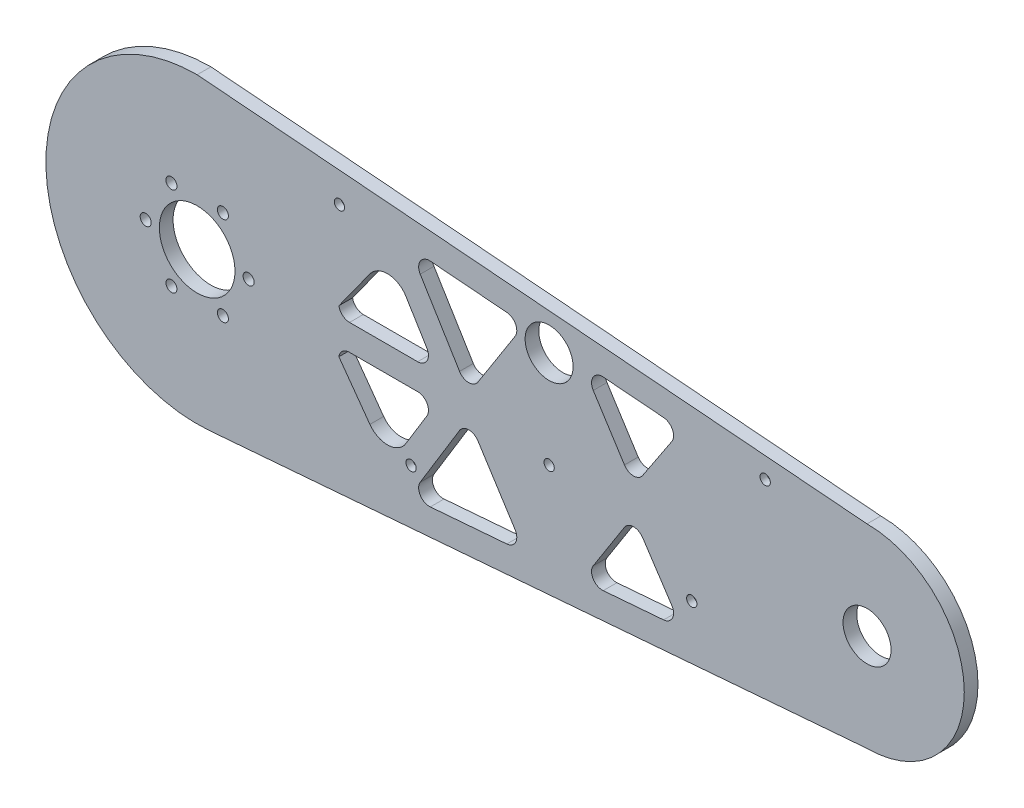
SolidWorks part; units mm, degrees
other "Marca1"
sketch "Croquis3" plane through (-70, -70, 6.35) normal (0, 0, 1) x (1, 0, 0)
material "6061-O (SS)"
ref_plane "Front Plane" through (0, 0, 0) normal (0, 0, 1) x (1, 0, 0)
ref_plane "Top Plane" through (0, 0, 0) normal (0, 1, 0) x (1, 0, 0)
ref_plane "Right Plane" through (0, 0, 0) normal (1, 0, 0) x (0, 0, -1)
sketch "Sketch1" plane through (0, 0, 0) normal (0, 0, 1) x (1, 0, 0)
  line L0 (0, 70) -> (310, 45)
  line L1 (5.1714, -69.8087) -> (310, -45)
  line L2 (0, 0) -> (310, 0) construction
  line L3 (107.899, 49.2595) -> (143.3142, 46.4034)
  line L4 (70.5232, 6) -> (102.03, 6)
  line L5 (219.6238, 32.8105) -> (206.1309, 12.4175)
  line L6 (197.7459, 12.4871) -> (183.2969, 35.1335)
  line L7 (162.8785, 6) -> (162.8785, -6) construction
  line L8 (258.6323, 64.5867) -> (258.6323, 39.5867) construction
  line L9 (147.1275, 38.7303) -> (129.9162, 11.7546)
  line L10 (121.433, 11.8395) -> (103.229, 41.6712)
  line L11 (98.117, 50.0484) -> (42.0027, 50.0484) construction
  line L12 (187.9139, 42.8067) -> (215.8558, 40.5533)
  line L13 (162.8785, 44.8257) -> (162.8785, 6) construction
  line L14 (67.1248, 64.5867) -> (162.8785, 40) construction
  line L15 (201.8849, 6) -> (201.8849, 41.68) construction
  line L16 (125.6066, 5) -> (125.6066, 47.8315) construction
  line L17 (96.5904, 29.5131) -> (106.2981, 13.6045)
  line L18 (125.6066, -5) -> (125.6066, -47.8315) construction
  line L19 (201.8849, -6) -> (201.8849, -41.68) construction
  line L20 (162.8785, -44.8257) -> (162.8785, -6) construction
  line L21 (98.117, -50.0484) -> (42.0027, -50.0484) construction
  line L22 (96.5904, -29.5131) -> (106.2981, -13.6045)
  line L23 (67.1248, 64.5867) -> (409.6974, 64.5867) construction
  line L24 (187.9139, -42.8067) -> (215.8558, -40.5533)
  line L25 (121.433, -11.8395) -> (103.229, -41.6712)
  line L26 (147.1275, -38.7303) -> (129.9162, -11.7546)
  line L27 (162.8785, 0) -> (258.6323, 64.5867) construction
  line L28 (67.1248, 64.5867) -> (67.1248, 39.5867) construction
  line L29 (197.7459, -12.4871) -> (183.2969, -35.1335)
  line L30 (219.6238, -32.8105) -> (206.1309, -12.4175)
  line L31 (70.5232, -6) -> (102.03, -6)
  line L32 (107.899, -49.2595) -> (143.3142, -46.4034)
  line L33 (0, -6.35) -> (0, 6.35) construction
  line L34 (67.1248, 39.5867) -> (162.8785, 40) construction
  line L35 (162.8785, 40) -> (68.3705, 24.1395) construction
  line L36 (79.9417, 30.1512) -> (65.583, 10.2294)
  line L37 (79.9417, -30.1512) -> (65.583, -10.2294)
  arc A0 (65.583, 10.2294) -> (70.5232, 6) centre (70.5232, 11) ccw
  arc A1 (310, -45) -> (310, 45) centre (310, 0) ccw
  circle A2 centre (0, 0) radius 14.2938
  circle A3 centre (310, 0) radius 11.115
  arc A4 (79.9417, 30.1512) -> (96.5904, 29.5131) centre (88.0542, 24.3041) cw
  arc A5 (96.5904, -29.5131) -> (79.9417, -30.1512) centre (88.0542, -24.3041) cw
  arc A6 (0, 70) -> (5.1714, -69.8087) centre (0, 0) ccw
  arc A7 (187.9139, 42.8067) -> (183.2969, 35.1335) centre (187.512, 37.8229) ccw
  arc A8 (219.6238, 32.8105) -> (215.8558, 40.5533) centre (215.4539, 35.5695) ccw
  arc A9 (206.1309, 12.4175) -> (197.7459, 12.4871) centre (201.961, 15.1765) cw
  circle A10 centre (162.8785, 40) radius 11.1125
  arc A13 (102.03, 6) -> (106.2981, 13.6045) centre (102.03, 11) ccw
  arc A14 (121.433, 11.8395) -> (129.9162, 11.7546) centre (125.7011, 14.444) ccw
  arc A15 (147.1275, 38.7303) -> (143.3142, 46.4034) centre (142.9123, 41.4196) ccw
  arc A16 (107.899, 49.2595) -> (103.229, 41.6712) centre (107.4971, 44.2757) ccw
  arc A17 (107.899, -49.2595) -> (103.229, -41.6712) centre (107.4971, -44.2757) cw
  arc A18 (147.1275, -38.7303) -> (143.3142, -46.4034) centre (142.9123, -41.4196) cw
  arc A19 (121.433, -11.8395) -> (129.9162, -11.7546) centre (125.7011, -14.444) cw
  arc A20 (102.03, -6) -> (106.2981, -13.6045) centre (102.03, -11) cw
  arc A24 (206.1309, -12.4175) -> (197.7459, -12.4871) centre (201.961, -15.1765) ccw
  arc A25 (219.6238, -32.8105) -> (215.8558, -40.5533) centre (215.4539, -35.5695) cw
  arc A26 (187.9139, -42.8067) -> (183.2969, -35.1335) centre (187.512, -37.8229) cw
  arc A29 (65.583, -10.2294) -> (70.5232, -6) centre (70.5232, -11) cw
  point P31 (177.8851, 43.6155)
  point P42 (187.6504, 6)
  point P44 (88.7465, 42.3671)
  point P45 (138.1067, 6)
  point P79 (88.7465, -42.3671)
  point P100 (138.1067, -6)
  point P101 (187.6504, -6)
  point P102 (177.8851, -43.6155)
  point P104 (0, 0)
  point P114 (310, 0)
  point P119 (0.2114, 0.3175)
  dimension "D2" = 45
  dimension "D3" = 12.7
  dimension "D4" = 22.23
  dimension "D6" = 12
  dimension "D11" = 5
  dimension "D12" = 70
  dimension "D13" = 25
  dimension "D8" = 5
  dimension "D14" = 12
  dimension "D15" = 25
  dimension "D16" = 310
  dimension "D17" = 22.225
  dimension "D5" = 28.5877
  dimension "D19" = 10
  dimension "D20" = 10
  dimension "D7" = 6
  dimension "D9" = 9.279
  dimension "D10" = 34
  dimension "D18" = 40
extrude "Boss-Extrude1" add sketch "Sketch1" along normal blind 6.35
sketch "Sketch2" plane through (0, 0, 6.35) normal (0, 0, 1) x (1, 0, 0)
  line L0 (263.0927, 39.4927) -> (-0.4655, 64.9983)
  line L1 (4.6885, -64.8307) -> (263.1366, -39.5384)
  arc A0 (-0.4655, 64.9983) -> (4.6885, -64.8307) centre (0, 0) ccw
  arc A1 (263.1366, -39.5384) -> (270.3186, -23.7999) centre (262.1626, -29.5859) ccw
  circle A2 centre (0, 0) radius 40
  arc A3 (270.292, 23.7623) -> (270.3186, -23.7999) centre (303.867, 0) ccw
  arc A4 (270.292, 23.7623) -> (263.0927, 39.4927) centre (262.1295, 29.5392) ccw
  dimension "D1" = 10
  dimension "D2" = 41.133
  dimension "D3" = 65
ref_plane "Plane1" through (0, 0, 10) normal (0, 0, 1) x (1, 0, 0)
sketch "Croquis1" plane through (0, 0, 6.35) normal (0, 0, 1) x (1, 0, 0)
  line L0 (5.1714, -69.8087) -> (310, -45) construction
  line L9 (100.6836, -22.8053) -> (88.7465, -42.3671) construction
  line L10 (96.5904, -29.5131) -> (106.2981, -13.6045) construction
  circle A1 centre (98.9956, -37.0901) radius 2.3813
  circle A2 centre (228.8774, -26.5196) radius 2.3813
  point P20 (0, 0)
  dimension "D5" = 4.7625
  dimension "D1" = 4.7625
extrude "Cortar-Extruir1" cut sketch "Croquis1" against normal blind 50
sketch "Croquis2" plane through (0, 0, 6.35) normal (0, 0, 1) x (1, 0, 0)
  circle A0 centre (98.9956, -37.0901) radius 5
  circle A1 centre (228.8774, -26.5196) radius 5
  dimension "D1" = 10
sketch "Croquis4" plane through (0, 0, 6.35) normal (0, 0, 1) x (1, 0, 0)
  line L0 (162.8785, 40) -> (162.8785, -40) construction
  line L1 (135.7539, -40) -> (190.0032, -40) construction
  circle A0 centre (162.8785, 0) radius 5
  point P8 (162.8785, -40)
  dimension "D1" = 10
  dimension "D2" = 40
sketch "Croquis6" plane through (0, 0, 6.35) normal (0, 0, 1) x (1, 0, 0)
  line L0 (98.9956, -37.0901) -> (228.8774, -26.5196) construction
  line L1 (228.8774, -26.5196) -> (262.8716, 39.2101) construction
  line L2 (98.9956, -37.0901) -> (65.8414, 50.869) construction
  circle A0 centre (65.8414, 50.869) radius 2.3813
  circle A1 centre (262.8716, 39.2101) radius 2.3813
  dimension "D5" = 4.7625
  dimension "D1" = 94
  dimension "D2" = 74
  dimension "D3" = 106
  dimension "D4" = 238
extrude "Cortar-Extruir6" cut sketch "Croquis6" against normal blind 10
sketch "Croquis7" plane through (0, 0, 6.35) normal (0, 0, 1) x (1, 0, 0)
  circle A0 centre (65.8414, 50.869) radius 5
  circle A1 centre (262.8716, 39.2101) radius 5
  dimension "D1" = 10
sketch "Croquis8" plane through (0, 0, 6.35) normal (0, 0, 1) x (1, 0, 0)
  circle A0 centre (0, 0) radius 17.5
  dimension "D1" = 35
extrude "Cortar-Extruir8" cut sketch "Croquis8" against normal blind 10
sketch "Croquis9" plane through (0, 0, 0) normal (0, 0, -1) x (-1, 0, 0)
  line L0 (0, 0) -> (23.8125, 0) construction
  circle A0 centre (0, 0) radius 23.8125 construction
  circle A1 centre (23.8125, 0) radius 2.5527
  circle A2 centre (11.9062, -20.6222) radius 2.5527
  circle A3 centre (-11.9063, -20.6222) radius 2.5527
  circle A4 centre (-23.8125, 0) radius 2.5527
  circle A5 centre (-11.9062, 20.6222) radius 2.5527
  circle A6 centre (11.9063, 20.6222) radius 2.5527
  point P17 (0, 0)
  dimension "D1" = 47.625
  dimension "D2" = 5.1054
  dimension "D3" = 6
extrude "Cortar-Extruir9" cut sketch "Croquis9" against normal blind 10
sketch "Croquis5" plane through (0, 0, 6.35) normal (0, 0, 1) x (1, 0, 0)
  circle A0 centre (162.8785, -5) radius 2.3813
  dimension "D1" = 4.7625
extrude "Cortar-Extruir5" cut sketch "Croquis5" against normal blind 10
sketch "Croquis10" plane through (0, 0, 0) normal (0, 0, -1) x (-1, 0, 0)
  circle A0 centre (-262.8716, 39.2101) radius 5
  circle A1 centre (-65.8414, 50.869) radius 5
  circle A2 centre (-162.8785, 0) radius 5
  circle A3 centre (-228.8774, -26.5196) radius 5
  circle A4 centre (-98.9956, -37.0901) radius 5
extrude "Cortar-Extruir10" cut sketch "Croquis10" against normal blind 3.18
